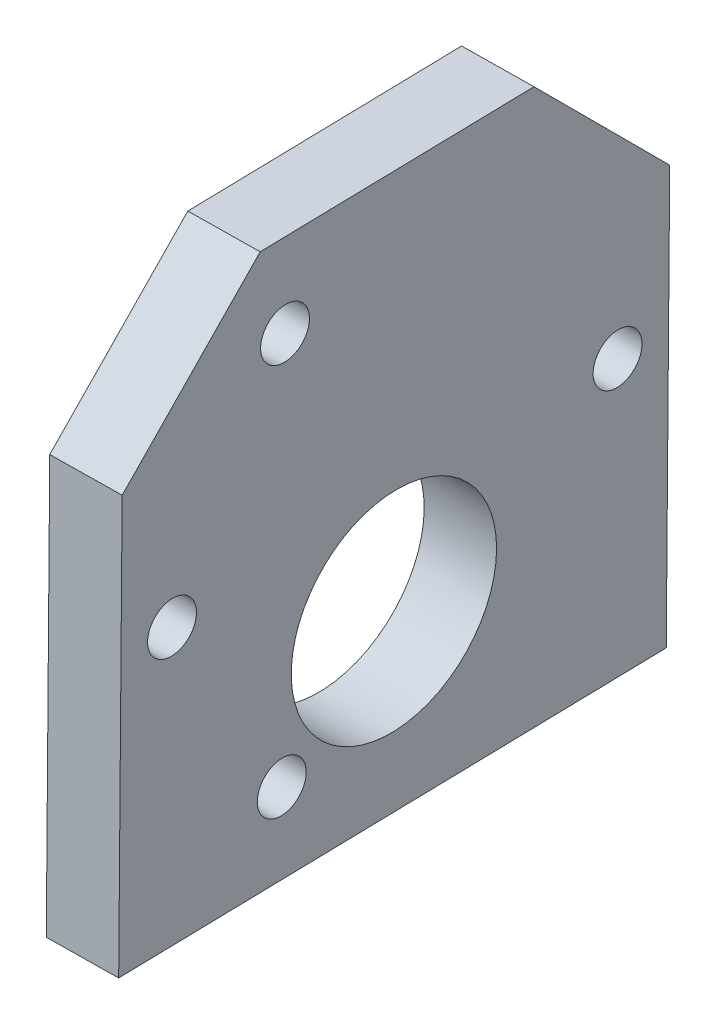
SolidWorks part; units mm, degrees
material "1060 Alloy"
ref_plane "Front" through (0, 0, 0) normal (0, 0, 1) x (1, 0, 0)
ref_plane "Top" through (0, 0, 0) normal (0, 1, 0) x (1, 0, 0)
ref_plane "Right" through (0, 0, 0) normal (1, 0, 0) x (0, 0, -1)
sketch "Sketch1" plane through (39.5296, -0.3237, -0.8516) normal (0.9997, -0.0082, -0.0215) x (-0.0215, 0.0001, -0.9998)
  line L1 (-19.05, 19.05) -> (19.05, 19.05)
  line L2 (-19.05, 19.05) -> (-19.05, -19.05)
  line L3 (-19.05, -19.05) -> (19.05, -19.05)
  line L4 (19.05, 19.05) -> (19.05, -19.05)
  line L5 (0, 19.05) -> (0, -19.05) construction
  circle A6 centre (0, -7.112) radius 7.1438
  point P1 (0, 0)
  point P4 (0, 0)
  point P5 (0, 0)
  point P7 (5.3162, 9.3806)
  point P10 (0, 0)
  point P12 (0, 0)
  point P13 (0, -8.3391)
  point P15 (0, -5.3516)
  dimension "D4" = 14.2875
  dimension "D5" = 7.112
  dimension "D1" = 38.1
  dimension "D2" = 19.05
  dimension "D3" = 19.05
extrude "Boss-Extrude1" add sketch "Sketch1" along normal blind 4.826
chamfer "Chamfer1" distance 9.525 angle 45 2 edges at (41.6877, 18.7076, -19.9509) (42.5083, 18.7042, 18.1403)
hole_wizard "M3 Clearance Hole1" positions "Sketch2" profile "Sketch3" hole size "M3" standard "ANSI Metric" end condition through all
sketch "Sketch2" plane through (44.3544, -0.3632, -0.9556) normal (0.9997, -0.0082, -0.0215) x (-0.0215, 0.0001, -0.9998)
  point P5 (15.5, -0.112)
  point P8 (-15.5, -0.112)
  point P11 (-7.75, -13.5354)
  point P14 (-7.75, 13.3114)
sketch "Sketch3" plane through (44.0196, -0.4739, -16.452) normal (0.021, 0.707, 0.707) x (-0.0094, 0.7072, -0.7069)
  line L0 (0, 0) -> (0, 5.9583)
  line L1 (0, 5.9583) -> (1.7, 5.9583)
  line L2 (1.7, 5.9583) -> (1.7, 0)
  line L5 (1.7, 0) -> (0, 0)
  line L11 (0, -6.35) -> (0, 107.95) construction
  dimension "Thru Hole Dia." = 3.4
  dimension "Thru Hole Depth" = 5.9583
